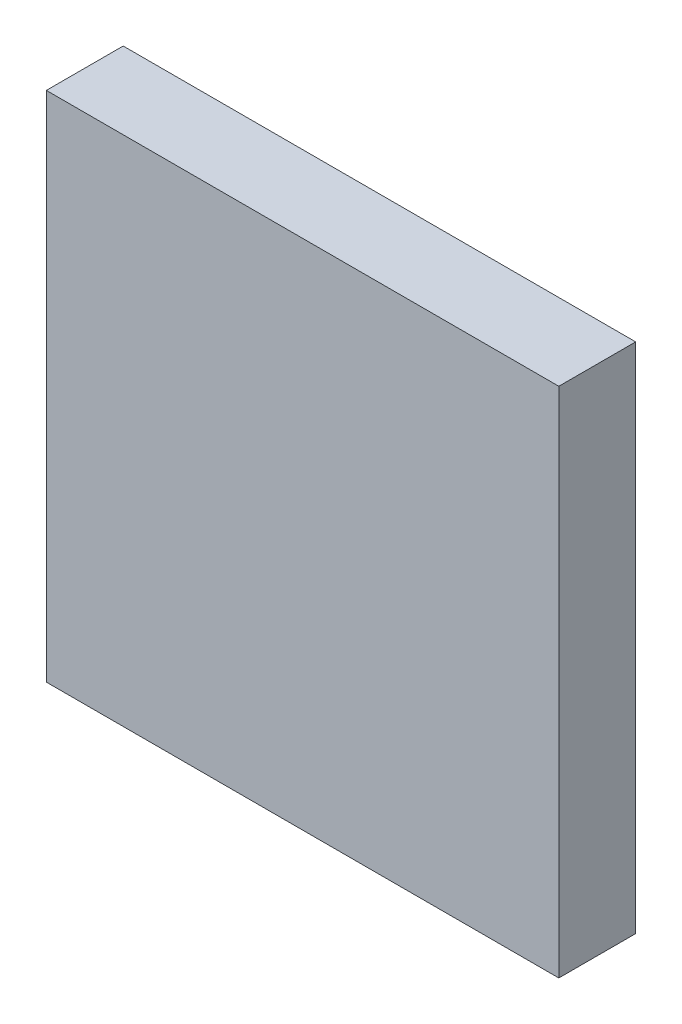
SolidWorks part; units mm, degrees
ref_plane "Alzado" through (0, 0, 0) normal (0, 0, 1) x (1, 0, 0)
ref_plane "Planta" through (0, 0, 0) normal (0, 1, 0) x (1, 0, 0)
ref_plane "Vista lateral" through (0, 0, 0) normal (1, 0, 0) x (0, 0, -1)
sketch "Croquis1" plane through (0, 0, 0) normal (0, 0, 1) x (1, 0, 0)
  line L1 (-5, 5) -> (5, 5)
  line L2 (-5, 5) -> (-5, -5)
  line L3 (-5, -5) -> (5, -5)
  line L4 (5, 5) -> (5, -5)
  line L5 (-5, 5) -> (5, -5) construction
  line L6 (-5, -5) -> (5, 5) construction
  point P0 (0, 0)
  dimension "D1" = 10
  dimension "D2" = 10
extrude "Saliente-Extruir6" add sketch "Croquis1" along normal blind 1.5
sketch "Croquis8" plane through (0, 0, 0) normal (1, 0, 0) x (0, 0, -1)
  line L0 (0, -5) -> (0, 5) construction
  line L1 (0, 3) -> (0, 1.5)
  line L2 (0, -1.5) -> (0, -3)
  arc A0 (0, -1.5) -> (0, 1.5) centre (0, 0) ccw
  arc A1 (0, -3) -> (0, 3) centre (0, 0) ccw
  dimension "D1" = 3
  dimension "D2" = 1.5
extrude "Saliente-Extruir7" add sketch "Croquis8" along normal blind 0.75 and the other way blind 0.75
